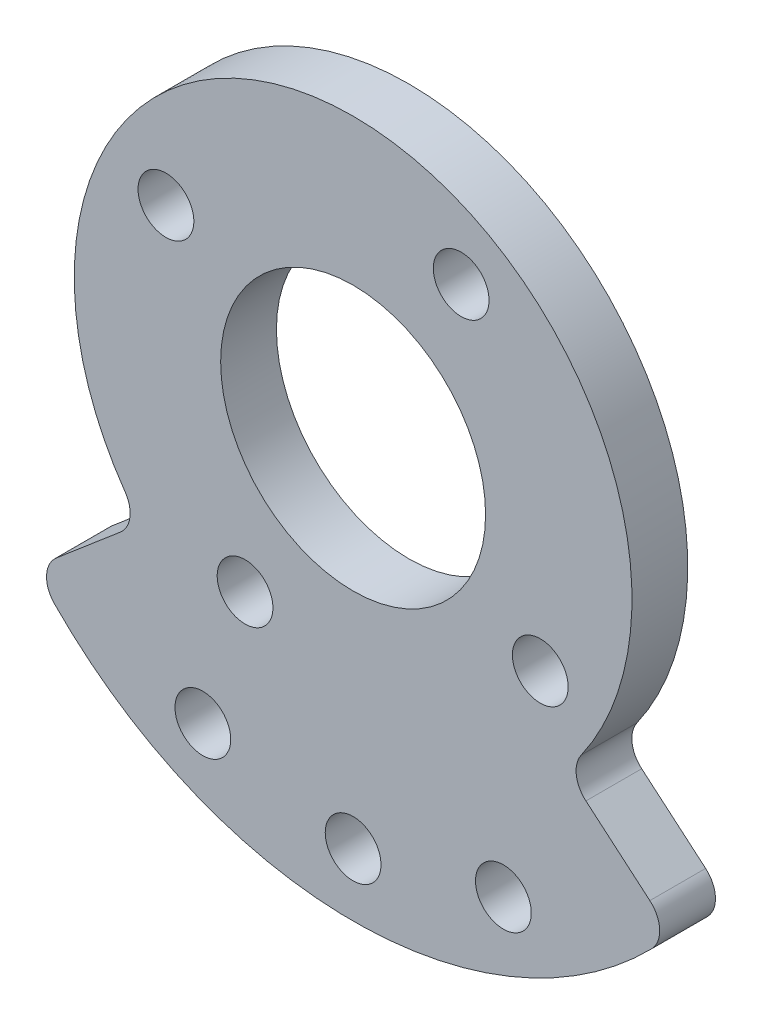
SolidWorks part; units mm, degrees
ref_plane "前视基准面" through (0, 0, 0) normal (0, 0, 1) x (1, 0, 0)
ref_plane "上视基准面" through (0, 0, 0) normal (0, 1, 0) x (1, 0, 0)
ref_plane "右视基准面" through (0, 0, 0) normal (1, 0, 0) x (0, 0, -1)
sketch "草图1" plane through (0, 0, 0) normal (0, 0, 1) x (1, 0, 0)
  line L0 (7.75, -13.4234) -> (-7.75, 13.4234)
  line L1 (0, 0) -> (0, 7.8753)
  circle A0 centre (0, 0) radius 20
  circle A2 centre (-15.5, 0) radius 2
  circle A3 centre (15.5, 0) radius 2
  circle A4 centre (-7.75, 13.4234) radius 2
  circle A5 centre (-7.75, -13.4234) radius 2
  circle A6 centre (7.75, -13.4234) radius 2
  circle A7 centre (7.75, 13.4234) radius 2
  dimension "D1" = 31
  dimension "D2" = 31
  dimension "D3" = 15.5
  dimension "D4" = 15.5
extrude "凸台-拉伸1" add sketch "草图1" along normal blind 4 contours A0 A5 A4 A3 A2 A6 A7 region at (-19.4343, 0, 0)
sketch "草图2" plane through (0, 0, 4) normal (0, 0, 1) x (1, 0, 0)
  line L2 (0, 0) -> (0, -13.6512)
  arc A0 (-31.6522, -31.6522) -> (31.6522, -31.6522) centre (0, 0) ccw
  arc A1 (-15.2406, -12.9509) -> (15.2406, -12.9509) centre (0, 0) ccw
  spline S0 degree 3 poles (-31.6522, -31.6522) (-33.3885, -22.6595) (-23.3924, -20.9627) (-16.1167, -16.1613) (-15.2406, -12.9509) knots 0 0 0 0 0.575012 0.868841 0.868841 0.868841 0.868841
  spline S1 degree 3 poles (31.6522, -31.6522) (33.3885, -22.6595) (23.3924, -20.9627) (16.1167, -16.1613) (15.2406, -12.9509) knots 0 0 0 0 0.575012 0.868841 0.868841 0.868841 0.868841
  circle M7 centre (0, 0) radius 20
extrude "凸台-拉伸2" add sketch "草图2" against normal blind 4 contours A0 S1 S0 M7 region at (0, -29.9614, 4)
fillet "圆角2" radius 5 1 edges at (-31.6522, -31.6522, 2)
fillet "圆角3" radius 5 1 edges at (31.6522, -31.6522, 2)
sketch "草图3" plane through (0, 0, 0) normal (0, 0, -1) x (-1, 0, 0)
  circle A0 centre (0, 0) radius 39.6045
  circle A1 centre (0, 0) radius 58.1601
extrude "切除-拉伸1" cut sketch "草图3" against normal blind 4
fillet "圆角4" radius 8 2 edges at (30.8758, -24.8032, 2) (-30.8758, -24.8032, 2)
sketch "草图4" plane through (0, 0, 0) normal (0, 0, -1) x (-1, 0, 0)
  line L0 (-22.1838, -32.8085) -> (-22.4053, -33.1361)
  line L1 (22.1838, -32.8085) -> (22.4686, -33.0933)
  arc A0 (-22.1838, -32.8085) -> (22.1838, -32.8085) centre (0, 0) ccw
  arc A1 (-22.4053, -33.1361) -> (22.4686, -33.0933) centre (0, 0) ccw
extrude "凸台-拉伸3" add sketch "草图4" against normal blind 4
sketch "草图5" plane through (0, 0, 0) normal (0, 0, -1) x (-1, 0, 0)
  circle A0 centre (-15.8482, -33.9865) radius 2
  circle A1 centre (0, -37.5) radius 2
  circle A2 centre (15.8482, -33.9865) radius 2
extrude "切除-拉伸2" cut sketch "草图5" against normal blind 4
sketch "草图6" plane through (0, 0, 0) normal (0, 0, -1) x (-1, 0, 0)
  circle A1 centre (0.0382, -30) radius 2
extrude "切除-拉伸3" cut sketch "草图6" against normal blind 10
sketch "草图7" plane through (0, 0, 4) normal (0, 0, 1) x (1, 0, 0)
  line L0 (-22.4686, -33.0933) -> (-23.9072, -34.5318)
  line L1 (22.4053, -33.1361) -> (23.5256, -34.7929)
  line L2 (-22.4686, -33.0933) -> (-22.1838, -32.8085)
  line L3 (22.4053, -33.1361) -> (22.1838, -32.8085)
  arc A0 (-23.9072, -34.5318) -> (23.5256, -34.7929) centre (0, 0) ccw
  arc A2 (-22.1838, -32.8085) -> (22.1838, -32.8085) centre (0, 0) ccw
extrude "凸台-拉伸4" add sketch "草图7" against normal blind 4
sketch "草图8" plane through (0, 0, 0) normal (0, 0, -1) x (-1, 0, 0)
  line L0 (-25.6784, -25.5584) -> (-20.5169, -32.8631)
  line L1 (-20.5169, -32.8631) -> (-23.5256, -34.7929)
  line L3 (20.5169, -32.8631) -> (23.5256, -34.7929)
  line L4 (25.6784, -25.5584) -> (20.5169, -32.8631)
  arc A0 (-21.1006, -18.9387) -> (-22.1838, -32.8085) centre (-17.7027, -26.1812) ccw construction
  spline S0 degree 2 poles (-23.5256, -34.7929) (-26.0018, -30.0563) (-25.6784, -25.5584) knots 0 0 0 0.479514 0.479514 0.479514
  spline S1 degree 2 poles (23.5256, -34.7929) (26.0018, -30.0563) (25.6784, -25.5584) knots 0 0 0 0.479514 0.479514 0.479514
extrude "凸台-拉伸6" add sketch "草图8" against normal blind 4
sketch "草图9" plane through (0, 0, 0) normal (0, 0, -1) x (-1, 0, 0)
  line L0 (23.7427, -34.3673) -> (22.9063, -35.2037)
  line L1 (22.9063, -35.2037) -> (24.4335, -34.375)
  line L2 (24.4335, -34.375) -> (23.7427, -34.3673)
  arc A0 (-23.5256, -34.7929) -> (23.9072, -34.5318) centre (0, 0) ccw construction
extrude "切除-拉伸6" cut sketch "草图9" against normal blind 4
fillet "圆角6" radius 10 1 edges at (23.5256, -34.7929, 2)
fillet "圆角7" radius 10 1 edges at (-23.7427, -34.3673, 2)
fillet "圆角8" radius 10 1 edges at (-22.9063, -35.2037, 2)
sketch "草图10" plane through (0, 0, 0) normal (0, 0, -1) x (-1, 0, 0)
  circle A0 centre (0.0382, -30) radius 2
  circle A1 centre (0, -37.5) radius 2
  circle A2 centre (15.8482, -33.9865) radius 2
  circle A3 centre (-15.8482, -33.9865) radius 2
extrude "凸台-拉伸7" add sketch "草图10" against normal blind 4
sketch "草图11" plane through (0, 0, 0) normal (0, 0, -1) x (-1, 0, 0)
  circle A0 centre (0, 0) radius 30
  circle A1 centre (0, 0) radius 55.3325
extrude "切除-拉伸7" cut sketch "草图11" against normal blind 4
sketch "草图12" plane through (0, 0, 0) normal (0, 0, -1) x (-1, 0, 0)
  line L0 (-15.2406, -12.9509) -> (-22.8609, -19.4263)
  line L1 (-15.2406, -12.9509) -> (-14.7679, -26.1134)
  line L3 (15.2406, -12.9509) -> (14.7679, -26.1134)
  line L4 (15.2406, -12.9509) -> (22.8609, -19.4263)
  arc A0 (-22.8609, -19.4263) -> (-14.7679, -26.1134) centre (0, 0) ccw
  arc A1 (14.7679, -26.1134) -> (22.8609, -19.4263) centre (0, 0) ccw
extrude "凸台-拉伸8" add sketch "草图12" against normal blind 4
sketch "草图13" plane through (0, 0, 0) normal (0, 0, -1) x (-1, 0, 0)
  circle A0 centre (-10.7768, -23.1108) radius 2
  circle A1 centre (0, -25.5) radius 2
  circle A2 centre (10.7768, -23.1108) radius 2
extrude "切除-拉伸8" cut sketch "草图13" against normal blind 4
sketch "草图14" plane through (0, 0, 0) normal (0, 0, -1) x (-1, 0, 0)
  circle A0 centre (0, 0) radius 9.5
  dimension "D1" = 19
extrude "切除-拉伸9" cut sketch "草图14" against normal blind 10
sketch "草图15" plane through (0, 0, 0) normal (0, 0, -1) x (-1, 0, 0)
  line L0 (0, 0) -> (13.4234, 7.75) construction
  line L1 (0, 0) -> (15.5, 0) construction
  arc A1 (9.5, 0) -> (8.2272, 4.75) centre (0, 0) ccw
  circle A3 centre (13.4234, 7.75) radius 2
  circle A4 centre (13.4234, -7.75) radius 2
  circle A5 centre (0, -15.5) radius 2
  circle A6 centre (-13.4234, -7.75) radius 2
  circle A7 centre (-13.4234, 7.75) radius 2
  circle A8 centre (0, 15.5) radius 2
  point P21 (0, 0)
  dimension "D1" = 30
  dimension "D2" = 6
extrude "凸台-拉伸9" add sketch "草图15" along normal blind 5 contours A8 | A5 | A7 | A3 | A4 | A6 region at (0, -15.5, 0) region at (13.4234, 7.75, 0) region at (0, 15.5, 0)
sketch "草图16" plane through (0, 0, 4) normal (0, 0, 1) x (1, 0, 0)
  circle A0 centre (0, 0) radius 9.5
  circle A1 centre (0, 0) radius 20
extrude "凸台-拉伸10" add sketch "草图16" against normal up to surface (4 mm away) up to face at (15.4234, -7.75, 0)
sketch "草图18" plane through (0, 0, -5) normal (0, 0, -1) x (-1, 0, 0)
  circle A1 centre (13.4234, 7.75) radius 2
  circle A6 centre (7.75, -13.4234) radius 2
  circle A7 centre (-13.4234, -7.75) radius 2
  circle A8 centre (-7.75, 13.4234) radius 2
  point P16 (0, 0)
  dimension "D1" = 4
extrude "切除-拉伸11" cut sketch "草图18" against normal through all
fillet "圆角9" radius 2 2 edges at (-15.2406, -12.9509, 2) (15.2406, -12.9509, 2)
fillet "圆角10" radius 2 2 edges at (-22.8609, -19.4263, 2) (22.8609, -19.4263, 2)
sketch "草图19" plane through (0, 0, -5) normal (0, 0, -1) x (-1, 0, 0)
  circle A0 centre (0, 15.5) radius 2
  circle A1 centre (0, -15.5) radius 2
  circle A2 centre (13.4234, -7.75) radius 2
  circle A3 centre (-13.4234, 7.75) radius 2
extrude "切除-拉伸12" cut sketch "草图19" against normal up to surface (5 mm away) up to face at (-5.75, -13.4234, 0)
